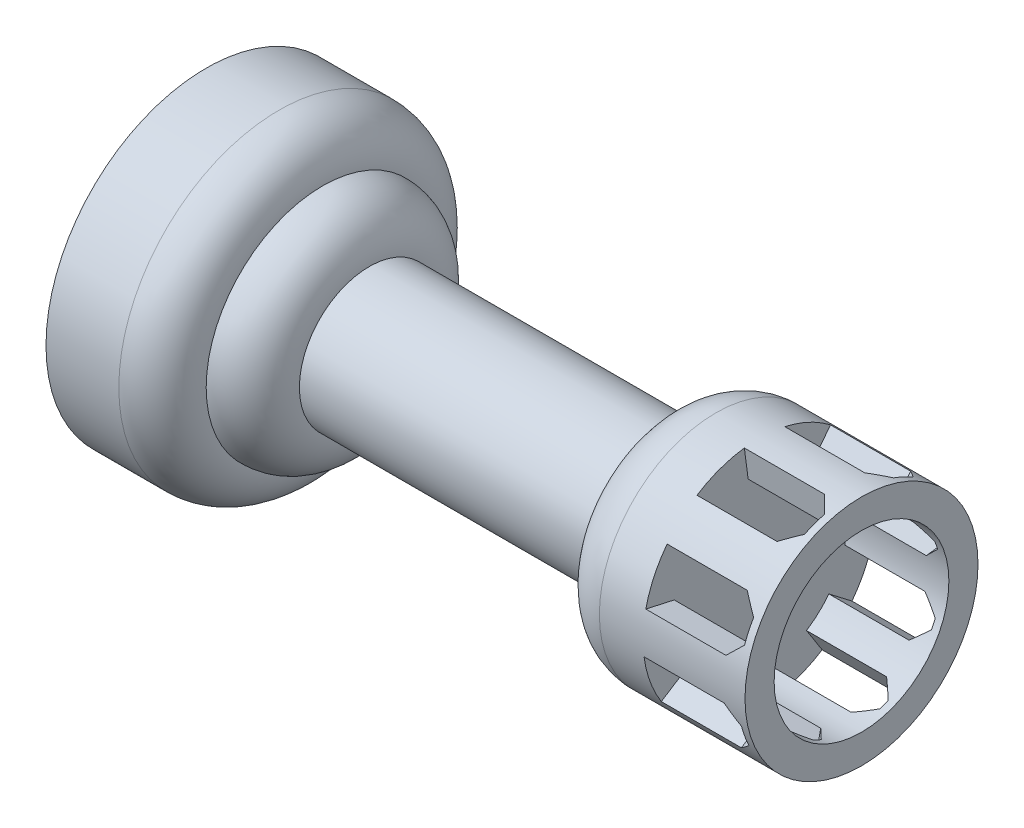
SolidWorks part; units mm, degrees
ref_plane "Спереди" through (0, 0, 0) normal (0, 0, 1) x (1, 0, 0)
ref_plane "Сверху" through (0, 0, 0) normal (0, 1, 0) x (1, 0, 0)
ref_plane "Справа" through (0, 0, 0) normal (1, 0, 0) x (0, 0, -1)
other "Configuration Table"
sketch "Эскиз1" plane through (0, 0, 0) normal (0, 1, 0) x (1, 0, 0)
  line L0 (0, 11) -> (38, 11) construction
  line L1 (0, 22) -> (5, 22)
  line L2 (0, 22) -> (0, 0)
  line L3 (0, 0) -> (5, 0)
  line L4 (5, 22) -> (5, 0)
  line L5 (5, 19) -> (8, 19)
  line L6 (5, 19) -> (5, 3)
  line L7 (5, 3) -> (8, 3)
  line L8 (8, 19) -> (8, 3)
  line L9 (8, 15.8) -> (35, 15.8)
  line L10 (8, 15.8) -> (8, 6.2)
  line L11 (8, 6.2) -> (35, 6.2)
  line L12 (35, 15.8) -> (35, 6.2)
  line L13 (35, 3) -> (38, 3)
  line L14 (35, 3) -> (35, 19)
  line L15 (35, 19) -> (38, 19)
  line L16 (38, 3) -> (38, 19)
  line L24 (38, 3) -> (45, 3)
  line L25 (38, 3) -> (38, 5)
  line L26 (38, 5) -> (45, 5)
  line L27 (45, 3) -> (45, 5)
  arc A0 (35, 3) -> (31.4652, 6.2) centre (35, 6.5523) cw
  arc A1 (8, 3) -> (11.2, 6.2) centre (8, 6.2) ccw
  arc A2 (5, 0) -> (8, 3) centre (5, 3) ccw
  dimension "D13" = 3.5523
  dimension "D14" = 7
  dimension "D15" = 3.2
  dimension "D17" = 3
  dimension "D1" = 22
  dimension "D2" = 5
  dimension "D3" = 3
  dimension "D4" = 3
  dimension "D5" = 3
  dimension "D6" = 27
  dimension "D7" = 3.2
  dimension "D8" = 3.2
  dimension "D9" = 3.2
  dimension "D10" = 3.2
  dimension "D11" = 3
  dimension "D12" = 16
  dimension "D16" = 2
revolve "Повернуть11" add sketch "Эскиз1" angle 360 about L0 region at (2.5, 0, -5.5) region at (6.5, 0, -7) region at (21.5, 0, -8.6) region at (36.5, 0, -7) region at (9.3581, 0, -4.8419) region at (33.5307, 0, -4.8526) region at (41.5, 0, -4)
sketch "Эскиз2" plane through (0, 0, 0) normal (-1, 0, 0) x (0, 0, 1)
  line L0 (50, 0) -> (-50, 0) construction
  line L1 (-22, 0) -> (0, 0) construction
  circle A0 centre (-11, 0) radius 10
  circle A1 centre (-11, 0) radius 11 construction
  dimension "D1" = 20
extrude "Вырез-Вытянуть1" cut sketch "Эскиз2" along direction (-1, 0, 0) on the side against the normal blind 2.5
sketch "Эскиз6" plane through (38, 0, 0) normal (1, 0, 0) x (0, 0, -1)
  line L0 (11, 0) -> (3.1896, 1.7315) construction
  line L1 (11, 0) -> (4.6532, 4.8701) construction
  line L2 (50, 0) -> (-50, 0) construction
  line L3 (4.6532, 4.8701) -> (6.2399, 3.6526)
  line L4 (3.1896, 1.7315) -> (5.1422, 1.2986)
  circle A2 centre (11, 0) radius 8 construction
  arc A5 (3.1896, 1.7315) -> (4.6532, 4.8701) centre (11, 0) cw
  arc A6 (5.1422, 1.2986) -> (6.2399, 3.6526) centre (11, 0) cw
  circle A8 centre (11, 0) radius 6 construction
  dimension "D1" = 12.5
  dimension "D2" = 25
extrude "Вырез-Вытянуть2" cut sketch "Эскиз6" along normal blind 6.5
sketch "Эскиз7" plane through (0, 0, 0) normal (1, 0, 0) x (0, 0, -1)
  line L0 (3, 0) -> (19, 0) construction
  line L1 (50, 0) -> (-50, 0) construction
  circle A0 centre (11, 0) radius 8 construction
pattern_circular "Круговой массив1" count 8 over 360 about axis through (45, 0, -11) along (-1, 0, 0) of "Вырез-Вытянуть2"
revolve "Повернуть12" add sketch "Эскиз1<12>" angle 360 about L0 region at (6.2732, 0, -1.7268)
sketch "Эскиз1<12>" plane through (0, 0, 0) normal (0, 1, 0) x (1, 0, 0) same geometry as "Эскиз1"
chamfer "Фаска4" distance 1 angle 45 2 edges at (44.5, 3.7611, -16.9037) (44.5, 0.9137, -17.9401)
chamfer "Фаска5" distance 1 angle 45 2 edges at (44.5, 5.5535, -15.2613) (44.5, 6.8341, -12.5151)
chamfer "Фаска6" distance 1 angle 45 12 edges at (44.5, -1.5151, -17.8341) (44.5, -4.2613, -16.5535) (44.5, -6.9401, -11.9137) (44.5, -5.9037, -14.7611) (44.5, -6.8341, -9.4849) (44.5, -5.5535, -6.7387) (44.5, -3.7611, -5.0963) (44.5, -0.9137, -4.0599) (44.5, 1.5151, -4.1659) (44.5, 4.2613, -5.4465) (44.5, 5.9037, -7.2389) (44.5, 6.9401, -10.0863)
sketch "Эскиз3" plane through (53, 0, 0) normal (1, 0, 0) x (0, 0, -1)
  line L0 (17, 0) -> (5, 0) construction
  line L1 (11, 0) -> (13.0706, 7.7274) construction
  line L2 (11, 0) -> (16.1423, 6.1284) construction
  line L3 (13.0706, 7.7274) -> (12.5529, 5.7956)
  line L4 (16.1423, 6.1284) -> (14.8567, 4.5963)
  line L5 (11, 0) -> (11, 8) construction
  circle A0 centre (11, 0) radius 6 construction
  circle A1 centre (11, 0) radius 6 construction
  circle A2 centre (11, 0) radius 8 construction
  arc A3 (13.0706, 7.7274) -> (16.1423, 6.1284) centre (11, 0) cw
  arc A4 (12.5529, 5.7956) -> (14.8567, 4.5963) centre (11, 0) cw
  dimension "D1" = 15
  dimension "D2" = 25
